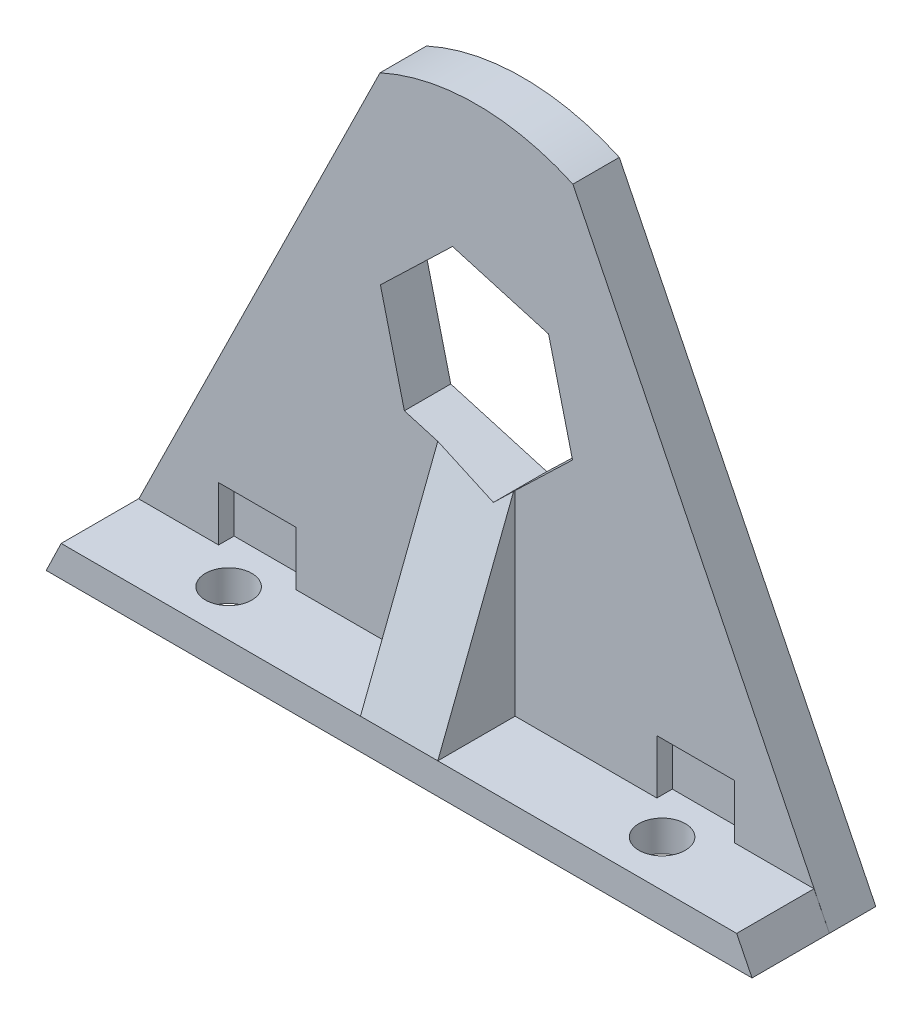
SolidWorks part; units mm, degrees
material "ABS"
ref_plane "前视基准面" through (0, 0, 0) normal (0, 0, 1) x (1, 0, 0)
ref_plane "上视基准面" through (0, 0, 0) normal (0, 1, 0) x (1, 0, 0)
ref_plane "右视基准面" through (0, 0, 0) normal (1, 0, 0) x (0, 0, -1)
sketch "草图1" plane through (0, 0, 0) normal (0, 0, 1) x (1, 0, 0)
  line L0 (0, 0) -> (0, -32.74) construction
  line L1 (-5.3822, 2.6518) -> (-22.8199, -32.74)
  line L2 (-22.8199, -32.74) -> (22.8199, -32.74)
  line L3 (5.3822, 2.6518) -> (22.8199, -32.74)
  circle A0 centre (0, 0) radius 3
  arc A1 (5.3822, 2.6518) -> (-5.3822, 2.6518) centre (0, 0) ccw
  dimension "D1" = 6
  dimension "D3" = 12
  dimension "D2" = 32.74
extrude "凸台-拉伸1" add sketch "草图1" along normal blind 2
sketch "草图2" plane through (0, 0, 2) normal (0, 0, 1) x (1, 0, 0)
  line L0 (21.8242, -30.74) -> (22.8199, -32.74)
  line L1 (-22.8199, -32.74) -> (22.8199, -32.74)
  line L3 (-21.8517, -30.74) -> (21.8242, -30.74)
  line L5 (-21.8517, -30.74) -> (-22.8199, -32.74)
extrude "凸台-拉伸2" add sketch "草图2" along normal blind 6
sketch "草图3" plane through (0, 0, 0) normal (1, 0, 0) x (0, 0, -1)
  line L0 (-2, -5.8523) -> (-8, -30.74)
  line L1 (-2, -32.74) -> (-2, 2.6518) construction
rib "筋2" sketch "草图3" sketch "草图3" thickness 5 extrusion direction parallel to sketch draft on no parameters "D1"=5
sketch "草图4" plane through (0, 0, 2) normal (0, 0, 1) x (1, 0, 0)
  circle A0 centre (0, 0) radius 4.1014
extrude "凸台-拉伸3" add sketch "草图4" against normal blind 2
sketch "草图9" plane through (0, 0, 0) normal (0, 0, -1) x (-1, 0, 0)
  line L0 (0, -12.74) -> (0, -32.74) construction
  line L1 (22.8199, -32.74) -> (-22.8199, -32.74) construction
  line L2 (-22.8199, -32.74) -> (22.8199, -32.74)
  line L3 (4.6626, -17.2203) -> (6.2114, -10.9422)
  line L4 (6.2114, -10.9422) -> (1.5488, -6.4619)
  line L5 (1.5488, -6.4619) -> (-4.6626, -8.2597)
  line L6 (-4.6626, -8.2597) -> (-6.2114, -14.5378)
  line L7 (-6.2114, -14.5378) -> (-1.5488, -19.0181)
  line L8 (-1.5488, -19.0181) -> (4.6626, -17.2203)
  line L9 (22.8199, -32.74) -> (13.9941, -7.2946)
  line L11 (-22.8199, -32.74) -> (-13.9941, -7.2946)
  circle A0 centre (0, -12.74) radius 5.6 construction
  arc A1 (14.3604, -8.3506) -> (-14.3604, -8.3506) centre (0, -12.74) ccw
  line M4 (-5.3822, 2.6518) -> (-22.8199, -32.74)
  line M5 (-22.8199, -32.74) -> (22.8199, -32.74)
  line M6 (22.8199, -32.74) -> (5.3822, 2.6518)
  dimension "D2" = 11.2
  dimension "D1" = 20
extrude "凸台-拉伸4" add sketch "草图9" against normal blind 3 contours A1 L8 L7 L6 L4 L3 M6 M4 M5 region at (0, -19.6321, 0)
sketch "草图11" plane through (0, 0, 3) normal (0, 0, 1) x (1, 0, 0)
  line L0 (0, -32.74) -> (0, -12.74) construction
  line L1 (-22.8199, -32.74) -> (22.8199, -32.74) construction
  line L3 (6.2114, -14.5378) -> (4.6626, -8.2597)
  line L4 (4.6626, -8.2597) -> (-1.5488, -6.4619)
  line L5 (-1.5488, -6.4619) -> (-6.2114, -10.9422)
  line L6 (-6.2114, -10.9422) -> (-4.6626, -17.2203)
  line L7 (-4.6626, -17.2203) -> (1.5488, -19.0181)
  line L8 (1.5488, -19.0181) -> (6.2114, -14.5378)
  circle A0 centre (0, -12.74) radius 5.6 construction
  dimension "D1" = 20
extrude "切除-拉伸1" cut sketch "草图11" against normal through all both and the other way through all
sketch "草图12" plane through (0, 0, 3) normal (0, 0, 1) x (1, 0, 0)
  line L0 (14.505, 2.7025) -> (10.2807, -1.7949)
  line L2 (-9.8502, -1.4059) -> (-13.4096, 3.6627)
  arc A0 (10.2807, -1.7949) -> (-9.8502, -1.4059) centre (0, -12.74) ccw
  arc A1 (14.505, 2.7025) -> (-13.4096, 3.6627) centre (0, -12.74) ccw
extrude "切除-拉伸2" cut sketch "草图12" against normal blind 10
sketch "草图13" plane through (-2.5, 0, 0) normal (-1, 0, 0) x (0, 0, 1)
  line L0 (3, -17.8463) -> (8, -30.74)
  line L1 (8, -30.74) -> (8, -17.8463)
  line L2 (8, -17.8463) -> (3.4065, -17.8463)
  line L3 (3.4065, -17.8463) -> (3, -17.8463)
extrude "切除-拉伸3" cut sketch "草图13" against normal blind 10
sketch "草图14" plane through (0, -32.74, 0) normal (0, -1, 0) x (1, 0, 0)
  circle A0 centre (14.0138, 5.0111) radius 1.5
  circle A1 centre (-14.0138, 5.0111) radius 1.5
extrude "切除-拉伸4" cut sketch "草图14" against normal blind 10
sketch "草图15" plane through (0, 0, 3) normal (0, 0, 1) x (1, 0, 0)
  line L0 (-21.8345, -30.74) -> (-2.5, -30.74) construction
  line L1 (-16.6741, -30.74) -> (-11.6629, -30.74)
  line L2 (-16.6741, -30.74) -> (-16.6741, -27.2457)
  line L3 (-16.6741, -27.2457) -> (-11.6629, -27.2457)
  line L4 (-11.6629, -30.74) -> (-11.6629, -27.2457)
  line L5 (0, -9.5013) -> (0, -3.4715) construction
  line L6 (11.6629, -30.74) -> (11.6629, -27.2457)
  line L7 (16.6741, -27.2457) -> (11.6629, -27.2457)
  line L8 (16.6741, -30.74) -> (16.6741, -27.2457)
  line L9 (16.6741, -30.74) -> (11.6629, -30.74)
extrude "切除-拉伸5" cut sketch "草图15" against normal blind 1
